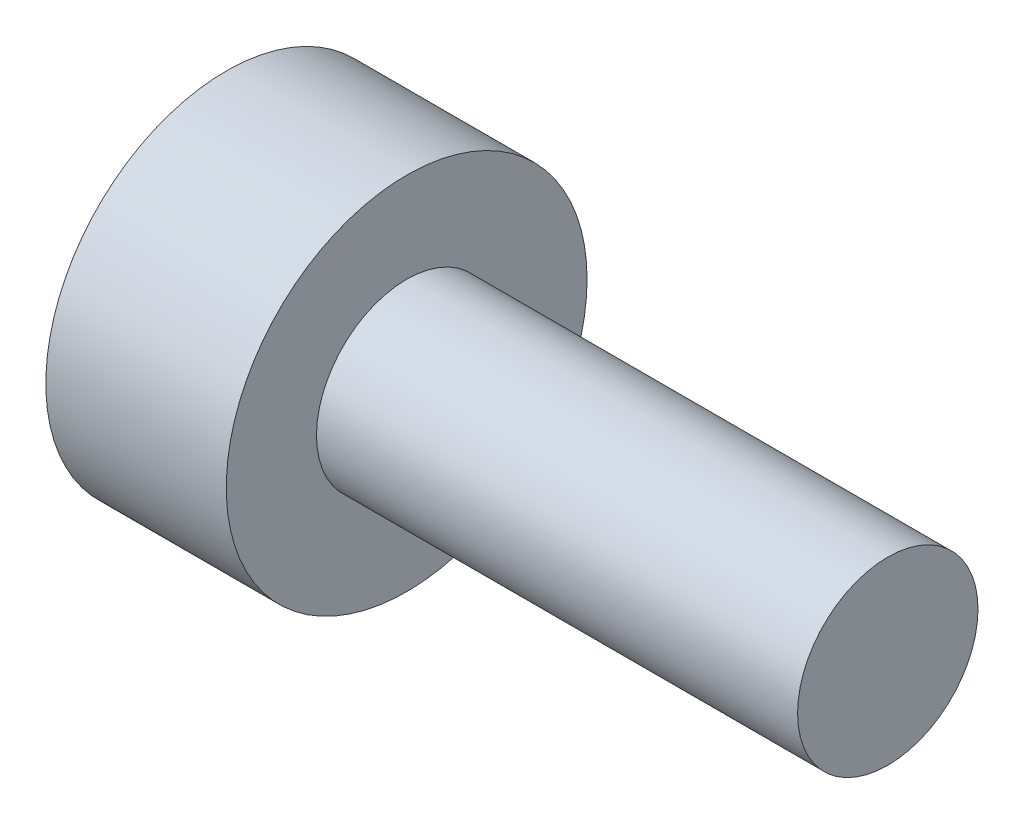
SolidWorks part; units mm, degrees
material "AISI 1045 Steel, cold drawn"
ref_plane "前视基准面" through (0, 0, 0) normal (0, 0, 1) x (1, 0, 0)
ref_plane "上视基准面" through (0, 0, 0) normal (0, 1, 0) x (1, 0, 0)
ref_plane "右视基准面" through (0, 0, 0) normal (1, 0, 0) x (0, 0, -1)
sketch "Sketch1" plane through (0, 0, 0) normal (1, 0, 0) x (0, 0, -1)
  circle A0 centre (0, 0) radius 3
  dimension "D1" = 6
extrude "Boss-Extrude1" add sketch "Sketch1" along normal blind 3
sketch "Sketch2" plane through (3, 0, 0) normal (1, 0, 0) x (0, 0, -1)
  circle A0 centre (0, 0) radius 1.5
  dimension "D1" = 3
extrude "Boss-Extrude2" add sketch "Sketch2" along normal blind 8
